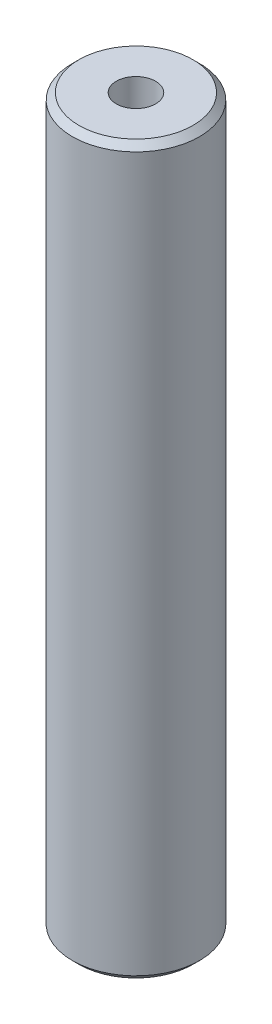
SolidWorks part; units mm, degrees
ref_plane "Front Plane" through (0, 0, 0) normal (0, 0, 1) x (1, 0, 0)
ref_plane "Top Plane" through (0, 0, 0) normal (0, 1, 0) x (1, 0, 0)
ref_plane "Right Plane" through (0, 0, 0) normal (1, 0, 0) x (0, 0, -1)
sketch "Sketch1" plane through (0, 0, 0) normal (0, 1, 0) x (1, 0, 0)
  circle A0 centre (0, 0) radius 25
  dimension "SHAFT_OD" = 50
extrude "Boss-Extrude1" add sketch "Sketch1" along normal blind 285.9294
sketch "Sketch2" plane through (0, 0, 0) normal (0, 1, 0) x (1, 0, 0)
  circle A0 centre (0, 0) radius 7.7367
  dimension "BORE_D" = 15.4734
extrude "Cut-Extrude1" cut sketch "Sketch2" along normal through all
chamfer "Chamfer1" distance 2.561 angle 45 2 edges at (0, 285.9294, 25) (0, 0, 25)
